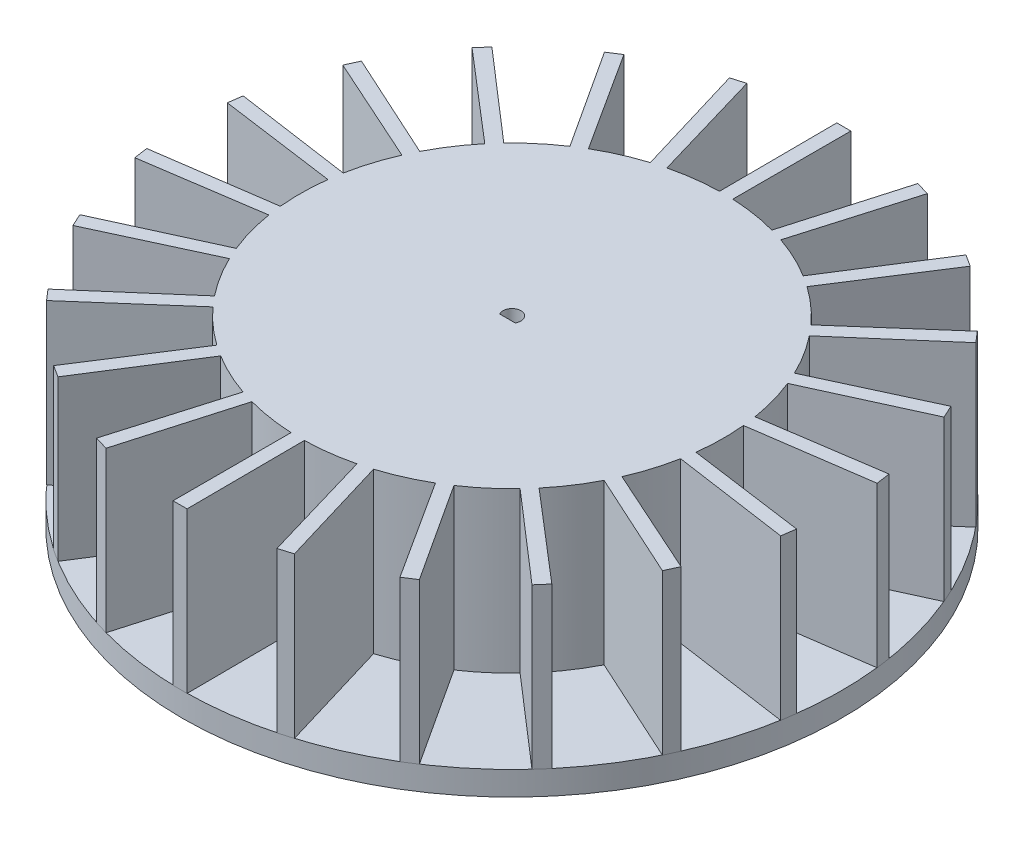
SolidWorks part; units mm, degrees
material "ABS"
ref_plane "Front Plane" through (0, 0, 0) normal (0, 0, 1) x (1, 0, 0)
ref_plane "Top Plane" through (0, 0, 0) normal (0, 1, 0) x (1, 0, 0)
ref_plane "Right Plane" through (0, 0, 0) normal (1, 0, 0) x (0, 0, -1)
sketch "Sketch1" plane through (0, 0, 0) normal (0, 1, 0) x (1, 0, 0)
  circle A0 centre (0, 0) radius 82.5
  dimension "D1" = 165
extrude "Boss-Extrude1" add sketch "Sketch1" along normal blind 6 contours A0
sketch "Sketch2" plane through (0, 6, 0) normal (0, 1, 0) x (1, 0, 0)
  line L0 (-25.4879, -78.499) -> (-22.1085, -79.4913)
  line L1 (-2.3397, -52.9483) -> (-2.3397, -82.5)
  line L2 (1.0246, -52.9901) -> (1.1824, -82.5)
  line L3 (-2.3397, -82.5) -> (1.1824, -82.5)
  line L4 (-13.9459, -51.1323) -> (-22.1085, -79.4913)
  line L5 (-17.1622, -50.1444) -> (-25.4879, -78.499)
  line L6 (-46.5711, -68.1385) -> (-43.6082, -70.0427)
  line L7 (-27.7866, -45.1321) -> (-43.6082, -70.0427)
  line L8 (-30.5943, -43.278) -> (-46.5711, -68.1385)
  line L9 (-63.8815, -52.2578) -> (-61.5751, -54.9196)
  line L10 (-39.3762, -35.4755) -> (-61.5751, -54.9196)
  line L11 (-41.5479, -32.9056) -> (-63.8815, -52.2578)
  line L12 (-76.0166, -32.1435) -> (-74.5535, -35.3473)
  line L13 (-47.7758, -22.9449) -> (-74.5535, -35.3473)
  line L14 (-49.1354, -19.8673) -> (-76.0166, -32.1435)
  line L15 (-81.9932, -9.4251) -> (-81.492, -12.9113)
  line L16 (-52.3049, -8.5555) -> (-81.492, -12.9113)
  line L17 (-52.7424, -5.2195) -> (-81.9932, -9.4251)
  line L18 (-81.3273, 14.0569) -> (-81.8285, 10.5706)
  line L19 (-52.5966, 6.5271) -> (-81.8285, 10.5706)
  line L20 (-52.0764, 9.8512) -> (-81.3273, 14.0569)
  line L21 (-74.0727, 36.4) -> (-75.5358, 33.1962)
  line L22 (-48.6271, 21.0808) -> (-75.5358, 33.1962)
  line L23 (-47.1916, 24.1238) -> (-74.0727, 36.4)
  line L24 (-60.8172, 55.7942) -> (-63.1236, 53.1324)
  line L25 (-40.7182, 33.9268) -> (-63.1236, 53.1324)
  line L26 (-38.4835, 36.442) -> (-60.8172, 55.7942)
  line L27 (-42.6346, 70.6684) -> (-45.5975, 68.7642)
  line L28 (-29.5106, 44.0241) -> (-45.5975, 68.7642)
  line L29 (-26.6578, 45.8079) -> (-42.6346, 70.6684)
  line L30 (-20.998, 79.8173) -> (-24.3774, 78.8251)
  line L31 (-15.9122, 50.5549) -> (-24.3774, 78.8251)
  line L32 (-12.6723, 51.4627) -> (-20.998, 79.8173)
  line L33 (2.3397, 82.5) -> (-1.1824, 82.5)
  line L34 (-1.0246, 52.9901) -> (-1.1824, 82.5)
  line L35 (2.3397, 52.9483) -> (2.3397, 82.5)
  line L36 (25.4879, 78.499) -> (22.1085, 79.4913)
  line L37 (13.9459, 51.1323) -> (22.1085, 79.4913)
  line L38 (17.1622, 50.1444) -> (25.4879, 78.499)
  line L39 (46.5711, 68.1385) -> (43.6082, 70.0427)
  line L40 (27.7866, 45.1321) -> (43.6082, 70.0427)
  line L41 (30.5943, 43.278) -> (46.5711, 68.1385)
  line L42 (63.8815, 52.2578) -> (61.5751, 54.9196)
  line L43 (39.3762, 35.4755) -> (61.5751, 54.9196)
  line L44 (41.5479, 32.9056) -> (63.8815, 52.2578)
  line L45 (76.0166, 32.1435) -> (74.5535, 35.3473)
  line L46 (47.7758, 22.9449) -> (74.5535, 35.3473)
  line L47 (49.1354, 19.8673) -> (76.0166, 32.1435)
  line L48 (81.9932, 9.4251) -> (81.492, 12.9113)
  line L49 (52.3049, 8.5555) -> (81.492, 12.9113)
  line L50 (52.7424, 5.2195) -> (81.9932, 9.4251)
  line L51 (81.3273, -14.0569) -> (81.8285, -10.5706)
  line L52 (52.5966, -6.5271) -> (81.8285, -10.5706)
  line L53 (52.0764, -9.8512) -> (81.3273, -14.0569)
  line L54 (74.0727, -36.4) -> (75.5358, -33.1962)
  line L55 (48.6271, -21.0808) -> (75.5358, -33.1962)
  line L56 (47.1916, -24.1238) -> (74.0727, -36.4)
  line L57 (60.8172, -55.7942) -> (63.1236, -53.1324)
  line L58 (40.7182, -33.9268) -> (63.1236, -53.1324)
  line L59 (38.4835, -36.442) -> (60.8172, -55.7942)
  line L60 (42.6346, -70.6684) -> (45.5975, -68.7642)
  line L61 (29.5106, -44.0241) -> (45.5975, -68.7642)
  line L62 (26.6578, -45.8079) -> (42.6346, -70.6684)
  line L63 (20.998, -79.8173) -> (24.3774, -78.8251)
  line L64 (15.9122, -50.5549) -> (24.3774, -78.8251)
  line L65 (12.6723, -51.4627) -> (20.998, -79.8173)
  circle A0 centre (0, 0) radius 82.5 construction
  arc A28 (-13.9459, -51.1323) -> (-2.3397, -52.9483) centre (0, 0) ccw
  arc A29 (1.0246, -52.9901) -> (12.6723, -51.4627) centre (0, 0) ccw
  arc A30 (15.9122, -50.5549) -> (26.6578, -45.8079) centre (0, 0) ccw
  arc A31 (29.5106, -44.0241) -> (38.4835, -36.442) centre (0, 0) ccw
  arc A32 (40.7182, -33.9268) -> (47.1916, -24.1238) centre (0, 0) ccw
  arc A36 (48.6271, -21.0808) -> (52.0764, -9.8512) centre (0, 0) ccw
  arc A37 (52.5966, -6.5271) -> (52.7424, 5.2195) centre (0, 0) ccw
  arc A40 (52.3049, 8.5555) -> (49.1354, 19.8673) centre (0, 0) ccw
  arc A42 (47.7758, 22.9449) -> (41.5479, 32.9056) centre (0, 0) ccw
  arc A44 (39.3762, 35.4755) -> (30.5943, 43.278) centre (0, 0) ccw
  arc A46 (27.7866, 45.1321) -> (17.1622, 50.1444) centre (0, 0) ccw
  arc A48 (13.9459, 51.1323) -> (2.3397, 52.9483) centre (0, 0) ccw
  arc A50 (-1.0246, 52.9901) -> (-12.6723, 51.4627) centre (0, 0) ccw
  arc A52 (-15.9122, 50.5549) -> (-26.6578, 45.8079) centre (0, 0) ccw
  arc A54 (-29.5106, 44.0241) -> (-38.4835, 36.442) centre (0, 0) ccw
  arc A56 (-40.7182, 33.9268) -> (-47.1916, 24.1238) centre (0, 0) ccw
  arc A58 (-48.6271, 21.0808) -> (-52.0764, 9.8512) centre (0, 0) ccw
  arc A60 (-52.5966, 6.5271) -> (-52.7424, -5.2195) centre (0, 0) ccw
  arc A62 (-52.3049, -8.5555) -> (-49.1354, -19.8673) centre (0, 0) ccw
  arc A64 (-47.7758, -22.9449) -> (-41.5479, -32.9056) centre (0, 0) ccw
  arc A66 (-39.3762, -35.4755) -> (-30.5943, -43.278) centre (0, 0) ccw
  arc A68 (-27.7866, -45.1321) -> (-17.1622, -50.1444) centre (0, 0) ccw
  circle A74 centre (0, 0) radius 50
  point P0 (0, 0)
  point P1 (0, -100)
  point P5 (-2.5, 0)
  point P7 (2.5, 0)
  point P110 (0, 0)
  dimension "D2" = 100
  dimension "D1" = 22
extrude "Boss-Extrude3" add sketch "Sketch2" along normal blind 40 contours L10 L9 L11 A64 L13 L12 L14 A62 L16 L15 L17 A60 L19 L18 L20 A58 L22 L21 L23 A56 L25 L24 L26 A54 L28 L27 L29 A52 L31 L30 L32 A50 L34 L33 L35 A48 L37 L36 L38 A46 L40 L39 L41 A44 L43 L42 L44 A42 L46 L45 L47 A40 L49 L48 L50 A37 L52 L51 L53 A36 L55 L54 L56 A32 L58 L57 L59 A31 L61 L60 L62 A30 L64 L63 L65 A29 L2 L3 L1 A28 L4 L0 L5 A68 L7 L6 L8 A66
sketch "Sketch12" plane through (0, 46, 0) normal (0, 1, 0) x (1, 0, 0)
  line L2 (-2.1347, -14.8473) -> (11.7908, -9.2724)
  line L3 (11.7908, -9.2724) -> (13.9255, 5.5749)
  line L4 (13.9255, 5.5749) -> (2.1347, 14.8473)
  line L5 (2.1347, 14.8473) -> (-11.7908, 9.2724)
  line L6 (-11.7908, 9.2724) -> (-13.9255, -5.5749)
  line L7 (-13.9255, -5.5749) -> (-2.1347, -14.8473)
  circle A1 centre (0, 0) radius 15 construction
sketch "Sketch14" plane through (0, 0, 0) normal (0, -1, 0) x (1, 0, 0)
  circle A0 centre (0, 0) radius 36
  dimension "D1" = 72
sketch "Sketch15" plane through (0, 46, 0) normal (0, 1, 0) x (1, 0, 0)
  line L0 (-1.9486, -1.125) -> (1.9486, -1.125)
  arc A0 (1.9486, -1.125) -> (-1.9486, -1.125) centre (0, 0) ccw
  dimension "D1" = 2.25
  dimension "D2" = 1.125
extrude "Cut-Extrude1" cut sketch "Sketch14" against normal blind 36 contours A0
extrude "Cut-Extrude2" cut sketch "Sketch15" against normal blind 36
